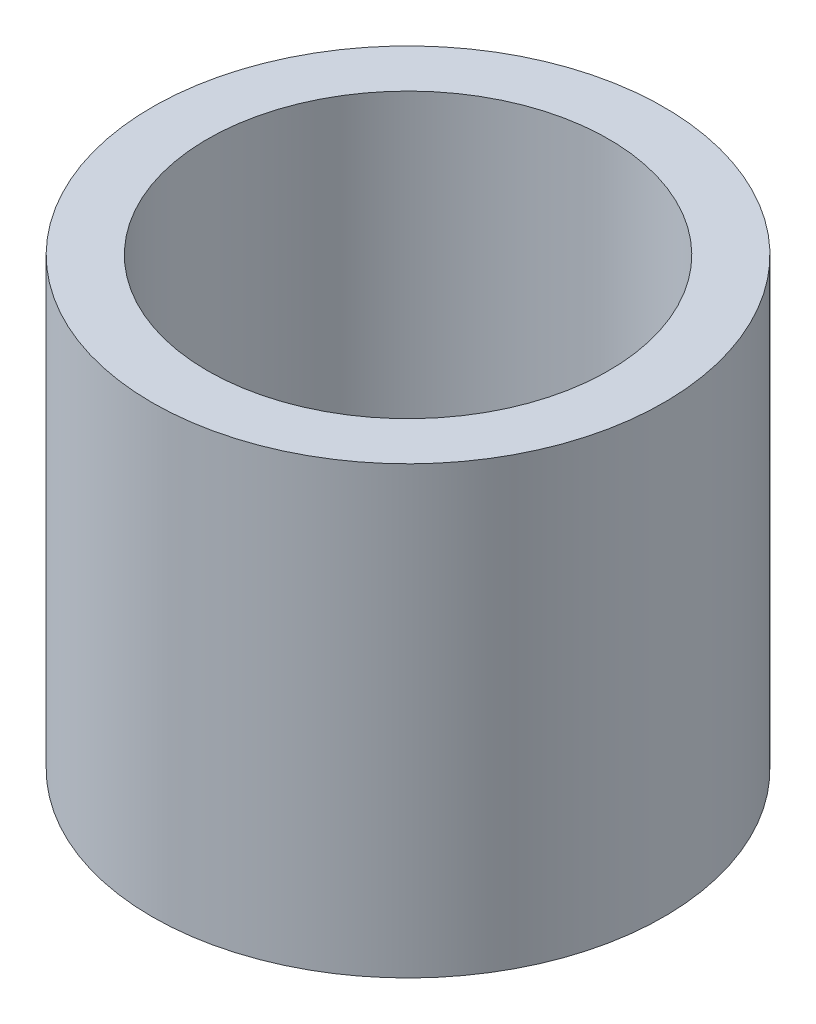
SolidWorks part; units mm, degrees
material "PET"
ref_plane "Front Plane" through (0, 0, 0) normal (0, 0, 1) x (1, 0, 0)
ref_plane "Top Plane" through (0, 0, 0) normal (0, 1, 0) x (1, 0, 0)
ref_plane "Right Plane" through (0, 0, 0) normal (1, 0, 0) x (0, 0, -1)
sketch "Sketch1" plane through (0, 0, 0) normal (0, 1, 0) x (1, 0, 0)
  circle A0 centre (0, 0) radius 3.175
  circle A1 centre (0, 0) radius 2.4892
  dimension "D1" = 6.35
  dimension "D2" = 4.9784
extrude "Boss-Extrude1" add sketch "Sketch1" along normal blind 5.5245
